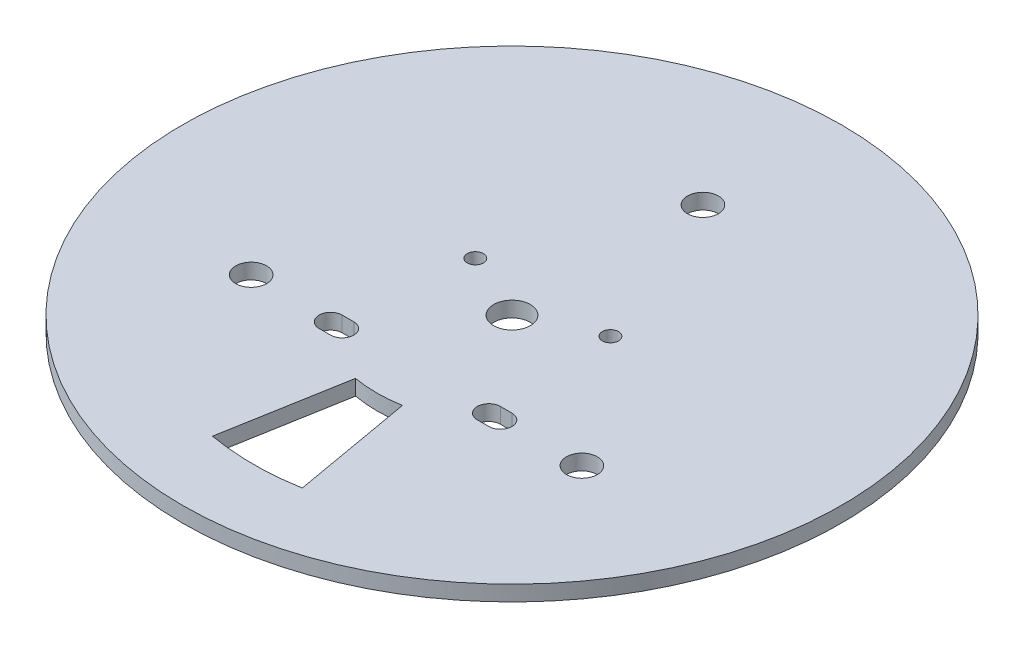
SolidWorks part; units mm, degrees
ref_plane "Plano frontal" through (0, 0, 0) normal (0, 0, 1) x (1, 0, 0)
ref_plane "Plano superior" through (0, 0, 0) normal (0, 1, 0) x (1, 0, 0)
ref_plane "Plano direito" through (0, 0, 0) normal (1, 0, 0) x (0, 0, -1)
sketch "Esboço1" plane through (0, 0, 0) normal (0, 1, 0) x (1, 0, 0)
  circle A0 centre (0, 0) radius 85.4
  dimension "D1" = 170.8
extrude "Ressalto-extrusão1" add sketch "Esboço1" along normal blind 4
sketch "Esboço3" plane through (0, 0, 0) normal (0, -1, 0) x (1, 0, 0)
  line L0 (11.9707, 32.8892) -> (22.9153, 62.9594) construction
  line L1 (-11.9707, 32.8892) -> (-22.9153, 62.9594) construction
  line L2 (6.0777, 34.4683) -> (11.6344, 65.9821)
  line L3 (0, 91.1664) -> (0, -117.3815) construction
  line L4 (-6.0777, 34.4683) -> (-11.6344, 65.9821)
  circle A1 centre (0, 0) radius 87.65
  circle A2 centre (0, 0) radius 87.65
  arc A3 (6.0777, 34.4683) -> (-6.0777, 34.4683) centre (0, 0) ccw
  arc A4 (11.6344, 65.9821) -> (-11.6344, 65.9821) centre (0, 0) ccw
  dimension "D2" = 70
  dimension "D3" = 134
  dimension "D4" = 20
  dimension "D5" = 20
  dimension "D6" = 10
  dimension "D7" = 10
  dimension "D1" = 0
extrude "Corte-extrusão2" cut sketch "Esboço3" against normal through all contours L2 A4 L4 A3
sketch "Esboço4" plane through (0, 4, 0) normal (0, 1, 0) x (1, 0, 0)
  circle A0 centre (42.8509, -24.74) radius 4
  circle A1 centre (0, 49.48) radius 4
  circle A2 centre (-42.8509, -24.74) radius 4
  point P0 (0, 49.48)
  point P2 (-42.8509, -24.74)
  point P4 (42.8509, -24.74)
extrude "Corte-extrusão3" cut sketch "Esboço4" against normal through all
sketch "Esboço5" plane through (0, 0, 0) normal (0, -1, 0) x (1, 0, 0)
  circle A1 centre (0, 0) radius 4.75
  dimension "D1" = 9.5
extrude "Corte-extrusão4" cut sketch "Esboço5" against normal through all
sketch "Esboço7" plane through (0, 4, 0) normal (0, 1, 0) x (1, 0, 0)
  line L0 (-22, -22) -> (-19, -22) construction
  line L1 (-19, -28) -> (-22, -28) construction
  line L2 (-22, -22) -> (-19, -22)
  line L3 (-19, -28) -> (-22, -28)
  line L4 (19, -28) -> (22, -28) construction
  line L5 (22, -22) -> (19, -22) construction
  line L6 (19, -28) -> (22, -28)
  line L7 (22, -22) -> (19, -22)
  arc A0 (-22, -22) -> (-22, -28) centre (-22, -25) ccw construction
  arc A1 (-19, -28) -> (-19, -22) centre (-19, -25) ccw construction
  arc A2 (-19, -28) -> (-19, -22) centre (-19, -25) ccw
  arc A3 (-22, -22) -> (-22, -28) centre (-22, -25) ccw
  arc A4 (19, -22) -> (19, -28) centre (19, -25) ccw construction
  arc A5 (22, -28) -> (22, -22) centre (22, -25) ccw construction
  arc A6 (19, -22) -> (19, -28) centre (19, -25) ccw
  arc A7 (22, -28) -> (22, -22) centre (22, -25) ccw
  circle A8 centre (-17.5, 8) radius 2.1 construction
  circle A9 centre (17.5, 8) radius 2.1 construction
  circle A10 centre (-17.5, 8) radius 2.1
  circle A11 centre (17.5, 8) radius 2.1
extrude "Corte-extrusão5" cut sketch "Esboço7" against normal through all
